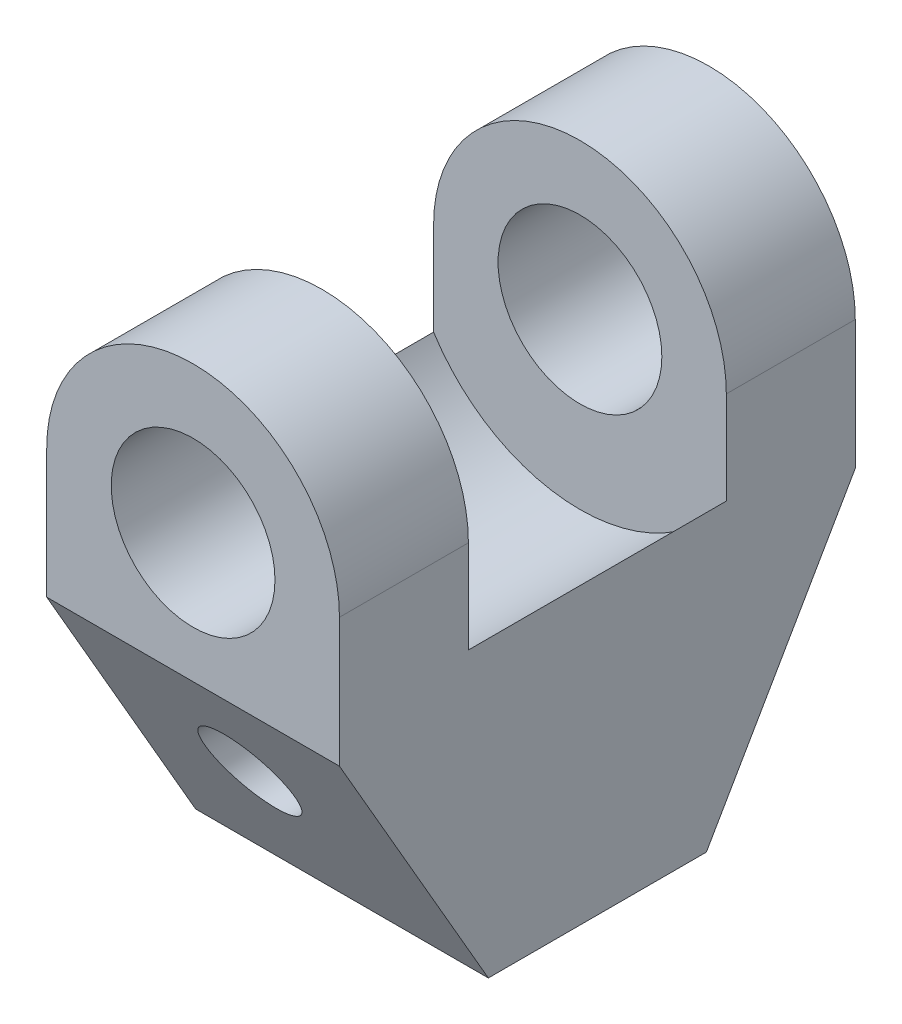
SolidWorks part; units mm, degrees
note: The reader was unsure of these and kept them because the rebuilt part matched: shared geometry of "Sketch2<3>", "Sketch2<4>".
material "ABS"
ref_plane "Front Plane" through (0, 0, 0) normal (0, 0, 1) x (1, 0, 0)
ref_plane "Top Plane" through (0, 0, 0) normal (0, 1, 0) x (1, 0, 0)
ref_plane "Right Plane" through (0, 0, 0) normal (1, 0, 0) x (0, 0, -1)
sketch "Sketch2" plane through (0, 0, 0) normal (0, 0, 1) x (1, 0, 0)
  line L2 (-11.35, 0) -> (-11.35, -30)
  line L3 (-11.35, -30) -> (11.35, -30)
  line L4 (11.35, 0) -> (11.35, -30)
  line L5 (4.2098, -15) -> (-5.7902, -15)
  line L6 (4.2098, -15) -> (4.2098, -30)
  line L7 (4.2098, -30) -> (-5.7902, -30)
  line L8 (-5.7902, -15) -> (-5.7902, -30)
  line L9 (4.2098, -15) -> (-5.7902, -30) construction
  line L10 (4.2098, -30) -> (-5.7902, -15) construction
  circle A0 centre (0, 0) radius 12.94 construction
  circle A1 centre (0, 0) radius 6.35
  arc A2 (11.35, 0) -> (-11.35, 0) centre (0, 0) ccw
  arc A3 (-11.35, -7.198) -> (11.35, -7.198) centre (0, 0) ccw
  circle A4 centre (0, 0) radius 11.35 construction
  circle A5 centre (-0.7902, -19) radius 1.5
  circle A6 centre (0, 0) radius 13.44 construction
  circle A7 centre (-0.7902, -19) radius 3.5
  point P10 (11.35, 0)
  point P12 (-0.7902, -22.5)
  point P13 (13.44, 0)
  dimension "D1" = 25.88
  dimension "D2" = 12.7
  dimension "D7" = 4
  dimension "3.5" = 3
  dimension "D4" = 30
  dimension "D6" = 15
  dimension "10" = 10
  dimension "D3" = 5
  dimension "D5" = 0.5
  dimension "D8" = 2
extrude "Boss-Extrude1" add sketch "Sketch2" along normal blind 10 contours L2 A3 L4 A2 A1 | A3 L2 L3 L8 L5 L6 L4 | L5 L8 L3 L6 A5
extrude "Boss-Extrude2" add sketch "Sketch2<3>" against normal blind 10 contours A3 L2 L3 L8 L5 L6 L4
sketch "Sketch2<3>" plane through (0, 0, 0) normal (0, 0, 1) x (1, 0, 0) same geometry as "Sketch2"
extrude "Boss-Extrude3" add sketch "Sketch2<4>" against normal blind 7.75 contours L5 L8 L3 L6 A5 | A7 A5
sketch "Sketch2<4>" plane through (0, 0, 0) normal (0, 0, 1) x (1, 0, 0) same geometry as "Sketch2"
chamfer "Chamfer1" distance 20 angle 30 1 edges at (0, -30, 10)
mirror "Mirror1" about plane through (0, 0, -10) normal (0, 0, 1) of bodies 103 104
